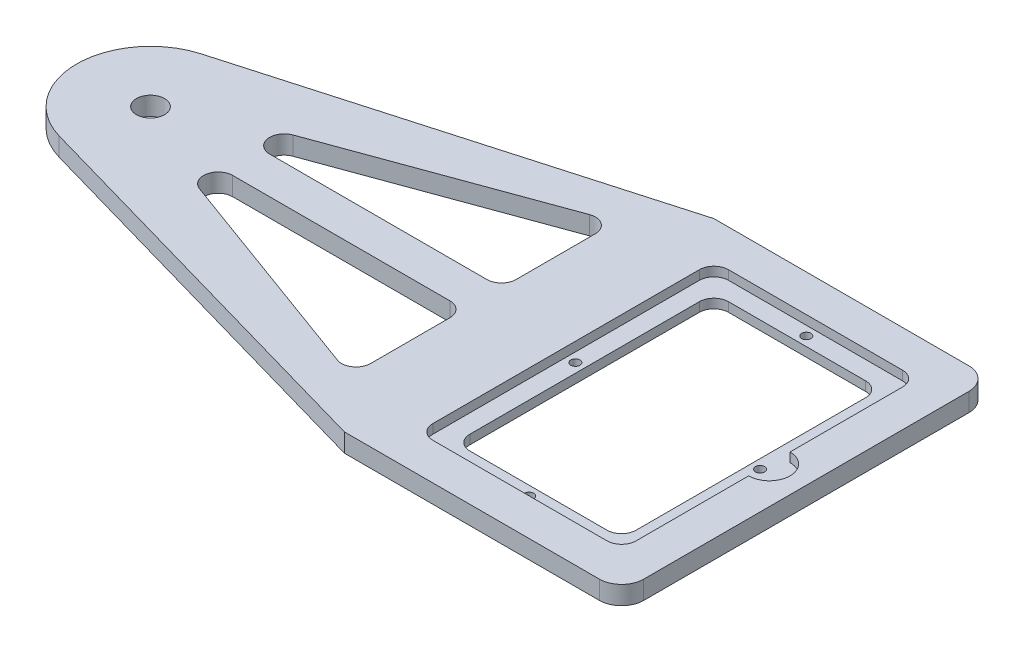
SolidWorks part; units mm, degrees
material "UHMW"
ref_plane "Front Plane" through (0, 0, 0) normal (0, 0, 1) x (1, 0, 0)
ref_plane "Top Plane" through (0, 0, 0) normal (0, 1, 0) x (1, 0, 0)
ref_plane "Right Plane" through (0, 0, 0) normal (1, 0, 0) x (0, 0, -1)
sketch "Sketch1" plane through (0, 0, 0) normal (0, 1, 0) x (1, 0, 0)
  line L0 (-47.625, 0) -> (47.625, 0) construction
  line L1 (-47.625, -63.5) -> (47.625, -63.5)
  line L2 (-47.625, -63.5) -> (-47.625, 63.5)
  line L3 (-47.625, 63.5) -> (47.625, 63.5)
  line L4 (47.625, -63.5) -> (47.625, 63.5)
  line L5 (-47.625, -63.5) -> (47.625, 63.5) construction
  line L6 (-47.625, 63.5) -> (47.625, -63.5) construction
  point P0 (0, 0)
  dimension "D1" = 95.25
  dimension "D2" = 127
  dimension "D3" = 63.5
extrude "Boss-Extrude1" add sketch "Sketch1" along normal blind 6.35
sketch "Sketch4" plane through (0, 6.35, 0) normal (0, 1, 0) x (1, 0, 0)
  line L1 (-47.625, 63.5) -> (-184.7599, 24.4278)
  line L5 (-47.625, 63.5) -> (-47.625, -63.5) construction
  line L9 (-47.625, -63.5) -> (-184.7599, -24.4278)
  line L10 (-47.625, 63.5) -> (-47.625, -63.5)
  arc A0 (-184.7599, 24.4278) -> (-184.7599, -24.4278) centre (-177.8, 0) ccw
  dimension "D1" = 50.8
  dimension "D2" = 177.8
extrude "Boss-Extrude3" add sketch "Sketch4" against normal blind 6.35
sketch "Sketch5" plane through (0, 6.35, 0) normal (0, 1, 0) x (1, 0, 0)
  circle A0 centre (-177.8, 0) radius 4.826
  circle A1 centre (-22.225, 0) radius 4.826
  arc A2 (-184.7599, 24.4278) -> (-184.7599, -24.4278) centre (-177.8, 0) ccw construction
  arc A3 (-184.7599, 24.4278) -> (-184.7599, -24.4278) centre (-177.8, 0) ccw
  dimension "D1" = 9.652
  dimension "D2" = 155.575
extrude "Cut-Extrude1" cut sketch "Sketch5" against normal through all contours A0 | A1 region at (-177.8, 6.35, 0) region at (-22.225, 6.35, 0)
sketch "Sketch6" plane through (0, 6.35, 0) normal (0, 1, 0) x (1, 0, 0)
  line L0 (-63.5, 6.35) -> (-63.5, -6.35) construction
  line L1 (-63.5, 45.7715) -> (-171.45, 6.35)
  line L2 (-171.45, 6.35) -> (-63.5, 6.35)
  line L3 (-63.5, 6.35) -> (-63.5, 45.7715)
  line L4 (-63.5, -6.35) -> (-63.5, -45.7715)
  line L5 (-63.5, -45.7715) -> (-171.45, -6.35)
  line L6 (-171.45, -6.35) -> (-63.5, -6.35)
  line L7 (0, 0) -> (-63.5, 0) construction
  line L8 (-47.625, 63.5) -> (-184.7599, 24.4278) construction
  line L9 (-203.2, 78.2466) -> (-203.2, -78.2466) construction
  arc A1 (-184.7599, 24.4278) -> (-184.7599, -24.4278) centre (-177.8, 0) ccw construction
  point P2 (0, 0)
  point P10 (-203.2, 0)
  dimension "D1" = 12.7
  dimension "D2" = 31.75
  dimension "D3" = 12.7
  dimension "D4" = 63.5
extrude "Cut-Extrude2" cut sketch "Sketch6" against normal through all
fillet "Fillet9" radius 5 6 edges at (-171.45, 3.175, 6.35) (-63.5, 3.175, 6.35) (-63.5, 3.175, 45.7715) (-63.5, 3.175, -6.35) (-171.45, 3.175, -6.35) (-63.5, 3.175, -45.7715)
sketch "Sketch7" plane through (0, 6.35, 0) normal (0, 1, 0) x (1, 0, 0)
  circle A0 centre (-22.225, 0) radius 5.4538
extrude "Boss-Extrude4" add sketch "Sketch7" against normal blind 6.35
sketch "Sketch8" plane through (0, 6.35, 0) normal (0, 1, 0) x (1, 0, 0)
  line L4 (-47.625, -63.5) -> (47.625, -63.5) construction
  line L5 (-34.925, 50.8) -> (-34.925, -50.8)
  line L7 (-47.625, 63.5) -> (-47.625, -63.5) construction
  line L8 (-184.7599, -24.4278) -> (-47.625, -63.5) construction
  line L10 (47.625, 50.8) -> (-47.625, 50.8)
  line L11 (34.925, 50.8) -> (-34.925, 50.8)
  line L13 (34.925, -63.5) -> (34.925, 63.5)
  line L14 (34.925, -50.8) -> (34.925, 50.8)
  line L15 (-34.925, 63.5) -> (-34.925, -63.5) construction
  line L16 (-47.625, -50.8) -> (47.625, -50.8)
  line L17 (-34.925, -50.8) -> (34.925, -50.8)
  dimension "D1" = 12.7
  dimension "D2" = 12.7
  dimension "D3" = 12.7
  dimension "D4" = 12.7
extrude "Cut-Extrude3" cut sketch "Sketch8" against normal blind 3.175
sketch "Sketch9" plane through (0, 3.175, 0) normal (0, 1, 0) x (1, 0, 0)
  line L14 (-28.575, -44.45) -> (28.575, -44.45)
  line L15 (28.575, -44.45) -> (28.575, 44.45)
  line L16 (-28.575, 44.45) -> (-28.575, -44.45)
  line L17 (28.575, 44.45) -> (-28.575, 44.45)
  line L18 (-28.575, -44.45) -> (28.575, -44.45)
  line L19 (28.575, -44.45) -> (28.575, 44.45)
  line L20 (-28.575, 44.45) -> (-28.575, -44.45)
  line L21 (28.575, 44.45) -> (-28.575, 44.45)
  dimension "D1" = 6.35
extrude "Cut-Extrude4" cut sketch "Sketch9" against normal through all
sketch "Sketch11" plane through (0, 3.175, 0) normal (0, 1, 0) x (1, 0, 0)
  line L0 (0, 50.8) -> (0, -50.8) construction
  line L1 (34.925, 50.8) -> (-34.925, 50.8) construction
  line L2 (-34.925, -50.8) -> (34.925, -50.8) construction
  line L3 (-34.925, 0) -> (34.925, 0) construction
  line L4 (-34.925, 50.8) -> (-34.925, -50.8) construction
  line L5 (34.925, -50.8) -> (34.925, 50.8) construction
  line L6 (-34.925, 50.8) -> (-34.925, -50.8) construction
  line L7 (-28.575, 44.45) -> (-28.575, -44.45) construction
  line L8 (34.925, 50.8) -> (-34.925, 50.8) construction
  circle A0 centre (-31.75, 0) radius 1.5875
  circle A1 centre (31.75, 0) radius 1.5875
  circle A2 centre (0, 47.625) radius 1.5875
  circle A3 centre (0, -47.625) radius 1.5875
  dimension "D1" = 3.175
  dimension "D4" = 3.175
  dimension "D2" = 3.175
  dimension "D3" = 3.175
  dimension "D5" = 3.175
extrude "Cut-Extrude6" cut sketch "Sketch11" against normal through all
sketch "Sketch12" plane through (0, 6.35, 0) normal (0, 1, 0) x (1, 0, 0)
  line L0 (34.925, -50.8) -> (34.925, 50.8) construction
  line L1 (34.925, 7.112) -> (34.925, 50.8) construction
  line L2 (34.925, -7.112) -> (34.925, -50.8) construction
  line L3 (34.925, 0) -> (-34.925, 0) construction
  line L4 (-34.925, 50.8) -> (-34.925, -50.8) construction
  line L5 (34.925, -50.8) -> (34.925, 50.8) construction
  line L6 (34.925, 7.112) -> (34.925, -7.112)
  arc A0 (34.925, 7.112) -> (34.925, -7.112) centre (34.925, 0) cw
  dimension "D1" = 7.112
extrude "Cut-Extrude7" cut sketch "Sketch12" against normal blind 3.175
fillet "Fillet10" radius 5 4 edges at (-34.925, 4.7625, 50.8) (34.925, 4.7625, 50.8) (34.925, 4.7625, -50.8) (-34.925, 4.7625, -50.8)
fillet "Fillet11" radius 5 4 edges at (-28.575, 1.5875, -44.45) (28.575, 1.5875, -44.45) (28.575, 1.5875, 44.45) (-28.575, 1.5875, 44.45)
fillet "Fillet12" radius 7.62 2 edges at (47.625, 3.175, -63.5) (47.625, 3.175, 63.5)
